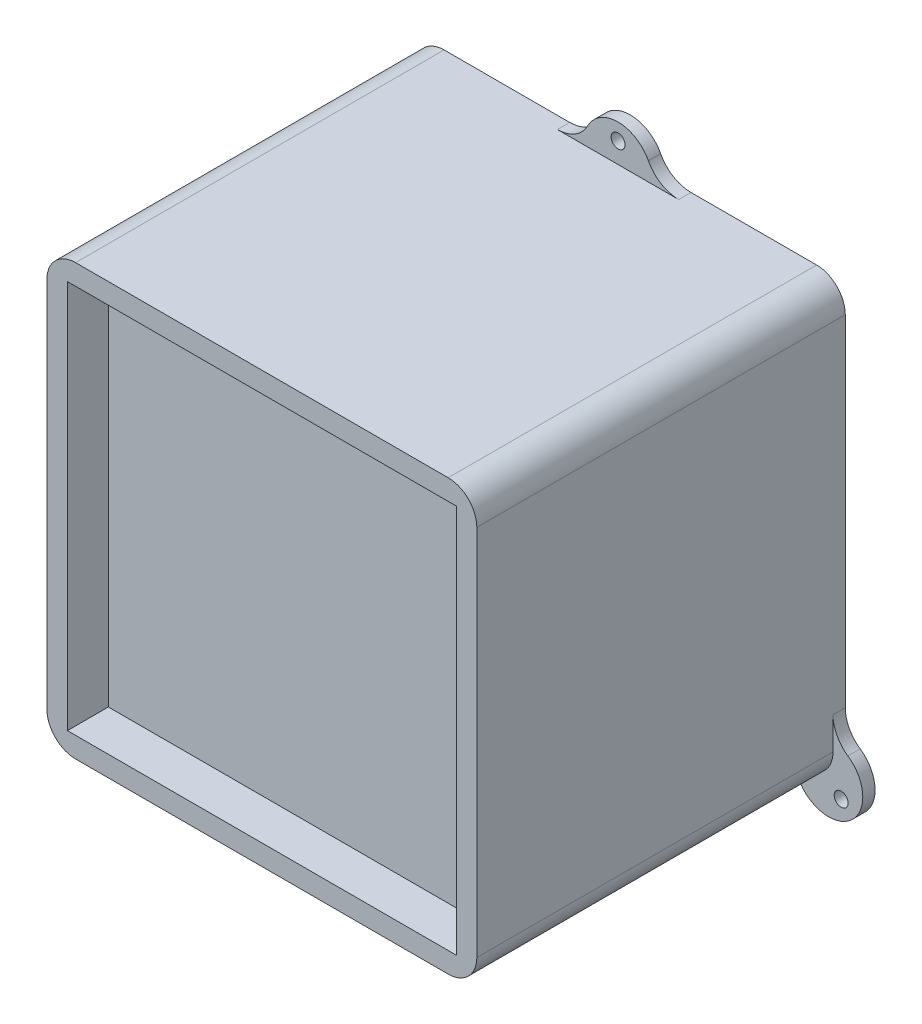
SolidWorks part; units mm, degrees
ref_plane "Plan de face" through (0, 0, 0) normal (0, 0, 1) x (1, 0, 0)
ref_plane "Plan de dessus" through (0, 0, 0) normal (0, 1, 0) x (1, 0, 0)
ref_plane "Plan de droite" through (0, 0, 0) normal (1, 0, 0) x (0, 0, -1)
sketch "Esquisse1" plane through (0, 0, 0) normal (0, 0, 1) x (1, 0, 0)
  line L1 (0, 0) -> (105, 0)
  line L2 (0, 0) -> (0, 105)
  line L3 (0, 105) -> (105, 105)
  line L4 (105, 0) -> (105, 105)
  dimension "D1" = 105
  dimension "D2" = 105
extrude "Boss.-Extru.1" add sketch "Esquisse1" along normal blind 80
sketch "Esquisse2" plane through (0, 0, 0) normal (0, 0, -1) x (-1, 0, 0)
  line L8 (-7, 7) -> (-7, 98)
  line L9 (-7, 98) -> (-98, 98)
  line L10 (-98, 98) -> (-98, 7)
  line L11 (-98, 7) -> (-7, 7)
  line L12 (-7, 7) -> (-7, 98)
  line L13 (-7, 98) -> (-98, 98)
  line L14 (-98, 98) -> (-98, 7)
  line L15 (-98, 7) -> (-7, 7)
  dimension "D1" = 7
extrude "Enlèv. mat.-Extru.1" cut sketch "Esquisse2" against normal offset from surface (70 mm away) 10 up to face at (52.5, 52.5, 80)
sketch "Esquisse3" plane through (0, 0, 80) normal (0, 0, 1) x (1, 0, 0)
  line L0 (100, 100) -> (5, 100)
  line L1 (5, 100) -> (5, 5)
  line L2 (5, 5) -> (100, 5)
  line L3 (100, 5) -> (100, 100)
  line L4 (0, 105) -> (0, 0)
  line L5 (0, 0) -> (105, 0)
  line L6 (105, 0) -> (105, 105)
  line L7 (105, 105) -> (0, 105)
  line L8 (0, 105) -> (0, 0)
  line L9 (0, 0) -> (105, 0)
  line L10 (105, 0) -> (105, 105)
  line L11 (105, 105) -> (0, 105)
  dimension "D1" = 0
  dimension "D2" = 5
extrude "Boss.-Extru.2" add sketch "Esquisse3" along normal blind 10
sketch "Esquisse4" plane through (0, 0, 0) normal (0, 0, -1) x (-1, 0, 0)
  line L0 (-98, 7) -> (-118.7207, -13.7207) construction
  line L1 (-7, 7) -> (8.1122, -8.1122) construction
  line L6 (0, 0) -> (-105, 0) construction
  line L7 (0.7972, -8.8596) -> (10.9788, 1.3219) construction
  line L8 (-114.7245, 0.0676) -> (-101.0769, -13.5799) construction
  line L9 (-52.5, 98) -> (-52.5, 115.4924) construction
  line L10 (-7, 98) -> (-98, 98) construction
  line L11 (-105, 105) -> (0, 105) construction
  line L12 (-62.0341, 114) -> (-40.7837, 114) construction
  line L13 (-49.1534, 98) -> (-55.8466, 98)
  circle A0 centre (-107, -2) radius 1.5
  circle A1 centre (2, -2) radius 1.5
  circle A2 centre (-1.0759, 1.0759) radius 8.35
  circle A3 centre (-103.9241, 1.0759) radius 8.35
  circle A4 centre (-52.5, 110) radius 1.5
  arc A5 (-49.1534, 98) -> (-55.8466, 98) centre (-52.5, 105.65) ccw
  point P28 (-52.5, 105)
  dimension "D1" = 3
  dimension "D4" = 3
  dimension "D7" = 16.7
  dimension "D8" = 16.7
  dimension "D10" = 3
  dimension "D12" = 16.7
  dimension "D2" = 2
  dimension "D3" = 4
  dimension "D5" = 2
  dimension "D6" = 4
  dimension "D9" = 5
  dimension "D11" = 4
extrude "Boss.-Extru.3" add sketch "Esquisse4" against normal blind 3
fillet "Congé1" radius 7 4 edges at (105, 0, 46.5) (0, 105, 45) (0, 0, 46.5) (105, 105, 45)
fillet "Congé3" [suppressed] radius 1 type face fillet
fillet "Congé4" radius 8.35 6 edges at (9.3563, 0, 1.5) (0, 9.3563, 1.5) (95.6437, 0, 1.5) (105, 9.3563, 1.5) (60.8247, 105, 1.5) (44.1753, 105, 1.5)
hole_wizard "Dégagement M31" positions "Esquisse5" profile "Esquisse6" hole size "M3" standard "ISO" end condition up to next
sketch "Esquisse5" plane through (0, 0, 3) normal (0, 0, 1) x (1, 0, 0)
  point P0 (107, -2)
  point P3 (-2, -2)
  point P6 (52.5, 110)
sketch "Esquisse6" plane through (107, -2, 3) normal (1, 0, 0) x (0, -1, 0)
  line L0 (0, 0) -> (0, 3)
  line L1 (0, 3) -> (1.7, 3)
  line L2 (1.7, 3) -> (1.7, 0)
  line L5 (1.7, 0) -> (0, 0)
  line L11 (0, -6.35) -> (0, 107.95) construction
  dimension "Diamètre du perçage jusqu'au prochain" = 3.4
  dimension "Profondeur du perçage jusqu'au prochain" = 3
